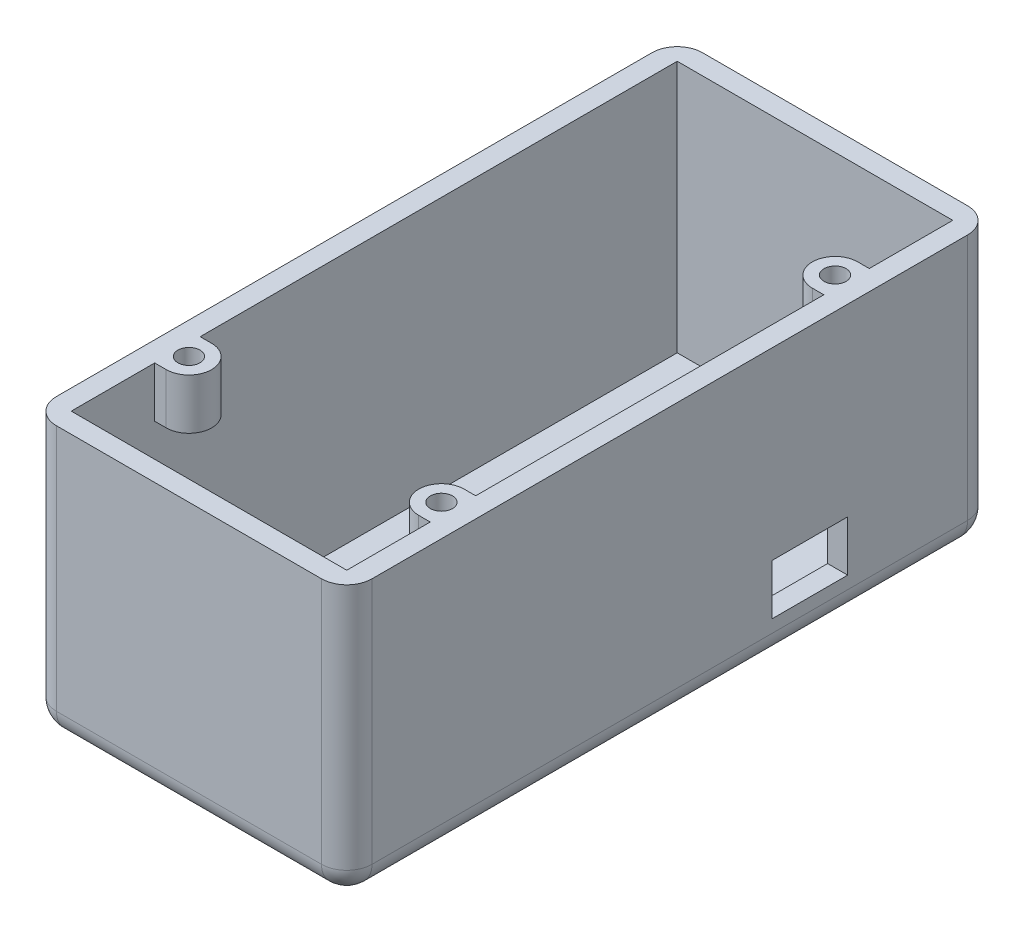
SolidWorks part; units mm, degrees
ref_plane "Front Plane" through (0, 0, 0) normal (0, 0, 1) x (1, 0, 0)
ref_plane "Top Plane" through (0, 0, 0) normal (0, 1, 0) x (1, 0, 0)
ref_plane "Right Plane" through (0, 0, 0) normal (1, 0, 0) x (0, 0, -1)
sketch "Sketch1" plane through (0, 0, 0) normal (0, 1, 0) x (1, 0, 0)
  line L1 (-25, 51.175) -> (25, 51.175)
  line L2 (-25, 51.175) -> (-25, -51.175)
  line L3 (-25, -51.175) -> (25, -51.175)
  line L4 (25, 51.175) -> (25, -51.175)
  line L5 (-25, 51.175) -> (25, -51.175) construction
  line L6 (-25, -51.175) -> (25, 51.175) construction
  line L7 (-21.825, 48) -> (21.825, 48)
  line L8 (-21.825, 48) -> (-21.825, -48)
  line L9 (-21.825, -48) -> (21.825, -48)
  line L10 (21.825, 48) -> (21.825, -48)
  line L11 (-21.825, 48) -> (21.825, -48) construction
  line L12 (-21.825, -48) -> (21.825, 48) construction
  point P0 (0, 0)
  point P6 (0, 0)
  dimension "D1" = 3.175
  dimension "D2" = 3.175
  dimension "D3" = 102.35
  dimension "D4" = 50
extrude "Boss-Extrude1" add sketch "Sketch1" along normal blind 40
sketch "Sketch2" plane through (0, 0, 0) normal (0, -1, 0) x (1, 0, 0)
  line L1 (25, -51.175) -> (-25, -51.175)
  line L2 (25, -51.175) -> (25, 51.175)
  line L3 (25, 51.175) -> (-25, 51.175)
  line L4 (-25, -51.175) -> (-25, 51.175)
extrude "Boss-Extrude2" add sketch "Sketch2" along normal blind 3.175
fillet "Fillet1" radius 4 8 edges at (25, 18.4125, 51.175) (25, 18.4125, -51.175) (-25, 18.4125, -51.175) (-25, 18.4125, 51.175) (0, -3.175, 51.175) (-25, -3.175, 0) (0, -3.175, -51.175) (25, -3.175, 0)
sketch "Sketch3" plane through (0, 0, 0) normal (0, 1, 0) x (1, 0, 0)
  line L0 (-21.825, -48) -> (21.825, -48) construction
  line L1 (-15, 30.05) -> (8.05, 30.05) construction
  line L2 (-15, 30.05) -> (-15, -28) construction
  line L3 (-15, -28) -> (8.05, -28) construction
  line L4 (8.05, 30.05) -> (8.05, -28) construction
  line L6 (-21, -47.175) -> (-21, 47.175) construction
  circle A0 centre (-15, 30.05) radius 1.3
  circle A1 centre (8.05, 30.05) radius 1.3
  circle A2 centre (8.05, -28) radius 1.3
  circle A3 centre (-15, -28) radius 1.3
  dimension "D2" = 2.6
  dimension "D1" = 58.05
  dimension "D3" = 23.05
  dimension "D4" = 20
  dimension "D5" = 6
extrude "Cut-Extrude1" cut sketch "Sketch3" against normal up to surface (3.175 mm away) up to face at (0, -3.175, 0)
sketch "Sketch4" plane through (0, 40, 0) normal (0, 1, 0) x (1, 0, 0)
  line L0 (-20, -27.575) -> (-21.825, -27.575)
  line L1 (-21.825, 48) -> (-21.825, -48) construction
  line L2 (-21.825, -27.575) -> (-21.825, -34.775)
  line L3 (-21.825, -34.775) -> (-20, -34.775)
  line L4 (0, -51.175) -> (0, 51.175) construction
  line L5 (-21, -51.175) -> (21, -51.175) construction
  line L6 (21, 51.175) -> (-21, 51.175) construction
  line L7 (-25, 47.175) -> (-25, -47.175) construction
  line L8 (21.825, -34.775) -> (20, -34.775)
  line L9 (21.825, -27.575) -> (21.825, -34.775)
  line L10 (20, -27.575) -> (21.825, -27.575)
  line L11 (-25, 0) -> (25, 0) construction
  line L12 (25, -47.175) -> (25, 47.175) construction
  line L13 (20, 27.575) -> (21.825, 27.575)
  line L14 (21.825, 27.575) -> (21.825, 34.775)
  line L15 (21.825, 34.775) -> (20, 34.775)
  arc A0 (-20, -34.775) -> (-20, -27.575) centre (-20, -31.175) ccw
  arc A1 (20, -34.775) -> (20, -27.575) centre (20, -31.175) cw
  arc A2 (20, 34.775) -> (20, 27.575) centre (20, 31.175) ccw
  dimension "D1" = 7.2
  dimension "D2" = 5
  dimension "D3" = 20
extrude "Boss-Extrude3" add sketch "Sketch4" against normal blind 8
sketch "Sketch5" plane through (0, 40, 0) normal (0, 1, 0) x (1, 0, 0)
  line L0 (0, 51.175) -> (0, -51.175) construction
  line L1 (21, 51.175) -> (-21, 51.175) construction
  line L2 (-21, -51.175) -> (21, -51.175) construction
  line L3 (-25, 0) -> (25, 0) construction
  line L4 (-25, 47.175) -> (-25, -47.175) construction
  line L5 (25, -47.175) -> (25, 47.175) construction
  circle A0 centre (-20, -31.175) radius 1.75
  circle A1 centre (20, -31.175) radius 1.75
  circle A2 centre (20, 31.175) radius 1.75
  dimension "D1" = 3.5
extrude "Cut-Extrude2" cut sketch "Sketch5" against normal blind 5
sketch "Sketch6" plane through (25, 0, 0) normal (1, 0, 0) x (0, 0, -1)
  line L0 (-47.175, 0.825) -> (47.175, 0.825) construction
  line L1 (28.175, 2.825) -> (16.175, 2.825)
  line L2 (28.175, 2.825) -> (28.175, 10.825)
  line L3 (28.175, 10.825) -> (16.175, 10.825)
  line L4 (16.175, 2.825) -> (16.175, 10.825)
  line L5 (47.175, 0.825) -> (47.175, 40) construction
  dimension "D1" = 2
  dimension "D2" = 19
  dimension "D3" = 8
  dimension "D4" = 12
extrude "Cut-Extrude3" cut sketch "Sketch6" against normal blind 10
